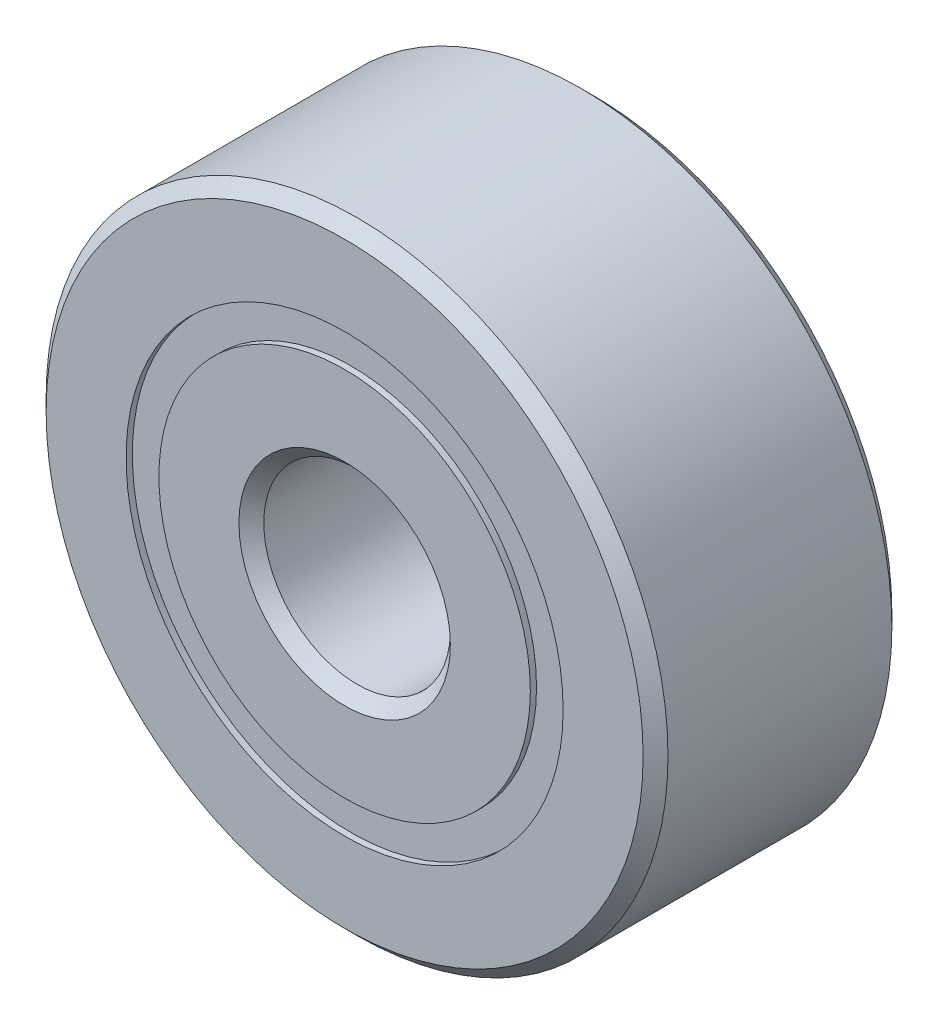
SolidWorks part; units mm, degrees
material "Alloy Steel"
ref_plane "Front Plane" through (0, 0, 0) normal (0, 0, 1) x (1, 0, 0)
ref_plane "Top Plane" through (0, 0, 0) normal (0, 1, 0) x (1, 0, 0)
ref_plane "Right Plane" through (0, 0, 0) normal (1, 0, 0) x (0, 0, -1)
sketch "Sketch1" plane through (0, 0, 0) normal (1, 0, 0) x (0, 0, -1)
  line L0 (-2, 0) -> (2, 0) construction
  line L1 (0, 5) -> (0, -5) construction
  line L2 (1.8, 5) -> (-1.8, 5)
  line L3 (-1.8, 5) -> (-2, 4.8)
  line L4 (-2, 4.8) -> (-2, 3.5137)
  line L5 (-2, 3.5137) -> (-0.8889, 3.5137)
  line L6 (2, 3.5137) -> (0.8889, 3.5137)
  line L7 (2, 4.8) -> (2, 3.5137)
  line L8 (1.8, 5) -> (2, 4.8)
  line L9 (0, 5) -> (0, 3.25) construction
  line L10 (0, 3.25) -> (0, 1.5) construction
  arc A0 (-0.8889, 3.5137) -> (0.8889, 3.5137) centre (0, 3.25) cw
  point P14 (0, 1.5)
  dimension "Width" = 4
  dimension "OD" = 10
  dimension "D1" = 45
  dimension "D2" = 0.2
  dimension "Shaft Dia" = 3
  dimension "D3" = 1.7778
  dimension "D4" = 0.2637
revolve "Revolve1" add sketch "Sketch1" angle 360 about L0
sketch "Sketch3" plane through (0, 0, 0) normal (1, 0, 0) x (0, 0, -1)
  line L0 (-2, 2.9863) -> (-0.8889, 2.9863)
  line L1 (0, 5) -> (0, -5) construction
  line L2 (-2, 4.8) -> (-2, 3.5137) construction
  line L3 (-2, 2.9863) -> (-2, 1.7)
  line L4 (-1.8, 5) -> (-2, 4.8) construction
  line L5 (-2, 1.7) -> (-1.8, 1.5)
  line L6 (-1.8, 1.5) -> (1.8, 1.5)
  line L7 (1.8, 5) -> (1.8, -5) construction
  line L8 (1.8, 1.5) -> (2, 1.7)
  line L9 (2, -4.8) -> (2, 4.8) construction
  line L10 (2, 1.7) -> (2, 2.9863)
  line L11 (2, 2.9863) -> (0.8889, 2.9863)
  line L13 (1.8, 5) -> (2, 4.8) construction
  arc A0 (0.8889, 3.5137) -> (-0.8889, 3.5137) centre (0, 3.25) ccw construction
  arc A1 (0.8889, 2.9863) -> (-0.8889, 2.9863) centre (0, 3.25) cw
revolve "Revolve3" add sketch "Sketch3" angle 360 about L0
sketch "Sketch4" plane through (0, 0, 0) normal (1, 0, 0) x (0, 0, -1)
  line L0 (-0.9272, 3.25) -> (0.9272, 3.25)
  arc A2 (-0.9272, 3.25) -> (0.9272, 3.25) centre (0, 3.25) cw
  arc A3 (0.8889, 3.5137) -> (-0.8889, 3.5137) centre (0, 3.25) ccw construction
revolve "Revolve4" add sketch "Sketch4" angle 360 about L0
ref_axis "Axis1" through (0, 0, -2) along (0, 0, 1)
pattern_circular "CirPattern1" count 12 every 30 about axis through (0, 0, -2) along (0, 0, 1) of bodies 104
sketch "Sketch5" plane through (0, 0, 0) normal (1, 0, 0) x (0, 0, -1)
  line L0 (-2, 3.5137) -> (-0.8889, 3.5137) construction
  line L1 (-1.9, 3.5137) -> (-0.9272, 3.5137)
  line L2 (-1.9, 3.5137) -> (-1.9, 2.9863)
  line L3 (-1.9, 2.9863) -> (-0.9272, 2.9863)
  line L4 (-0.9272, 3.5137) -> (-0.9272, 2.9863)
  line L5 (-2, 2.9863) -> (-0.8889, 2.9863) construction
  line L6 (2, 3.5137) -> (0.8889, 3.5137) construction
  line L7 (1.9, 3.5137) -> (0.9272, 3.5137)
  line L8 (1.9, 3.5137) -> (1.9, 2.9863)
  line L9 (1.9, 2.9863) -> (0.9272, 2.9863)
  line L10 (0.9272, 3.5137) -> (0.9272, 2.9863)
  line L11 (2, 2.9863) -> (0.8889, 2.9863) construction
  line L12 (-1.8, 5) -> (-2, 4.8) construction
  point P18 (-1.9, 4.9)
revolve "Revolve5" add sketch "Sketch5" angle 360 about L0
sketch "Sketch6" plane through (0, 0, 0) normal (1, 0, 0) x (0, 0, -1)
  line L0 (2, 0) -> (-2, 0) construction
  line L1 (2, 3.5137) -> (0.9, 3.5137)
  line L2 (2, 3.5137) -> (2, 9.5)
  line L3 (2, 9.5) -> (0.9, 9.5)
  line L4 (0.9, 3.5137) -> (0.9, 9.5)
  dimension "Th" = 1.1
  dimension "Flange OD" = 19
revolve "Revolve6" [suppressed] add sketch "Sketch6" angle 360 about L0
equation "\"D2@Sketch1\" = \"Width@Sketch1\"*.05"
equation "\"D3@Sketch1\" = \"Width@Sketch1\"/2.25"
equation "\"D4@Sketch1\" = (((\"OD@Sketch1\"-\"Width@Sketch1\")/2)/3.25)/3.5"
equation "\"D2@CirPattern1\" = 360/\"Balls@CirPattern1\""
